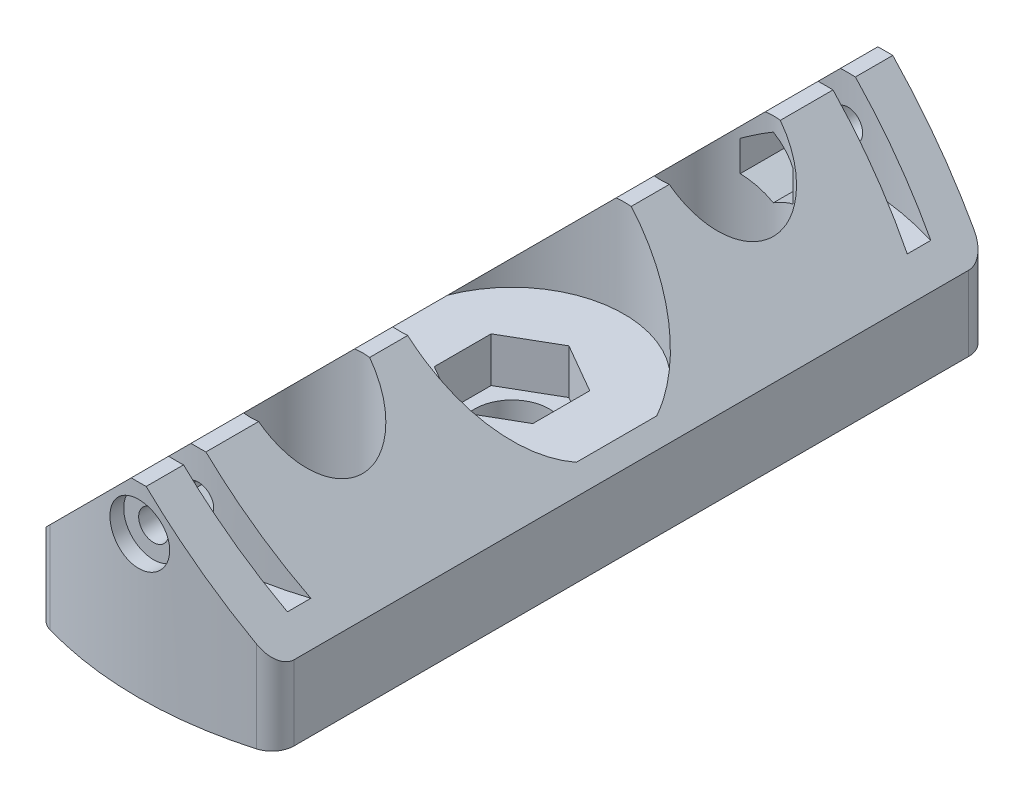
SolidWorks part; units mm, degrees
material "3D printed plastic"
ref_plane "Front Plane" through (0, 0, 0) normal (0, 0, 1) x (1, 0, 0)
ref_plane "Top Plane" through (0, 0, 0) normal (0, 1, 0) x (1, 0, 0)
ref_plane "Right Plane" through (0, 0, 0) normal (1, 0, 0) x (0, 0, -1)
sketch "Sketch1" plane through (0, 0, 0) normal (0, 1, 0) x (1, 0, 0)
  line L0 (0, 27.5) -> (0, -27.5) construction
  line L1 (-16, 45.1664) -> (-16, -45.1664)
  line L2 (16, 45.1664) -> (16, -45.1664)
  circle A0 centre (0, 0) radius 5
  circle A1 centre (0, -27.5) radius 6
  circle A2 centre (0, 27.5) radius 6
  arc A3 (13.8298, 48.0493) -> (-13.8298, 48.0493) centre (0, 0) ccw
  arc A4 (-13.8298, -48.0493) -> (13.8298, -48.0493) centre (0, 0) ccw
  arc A5 (16, -45.1664) -> (13.8298, -48.0493) centre (13, -45.1664) cw
  arc A6 (-16, -45.1664) -> (-13.8298, -48.0493) centre (-13, -45.1664) ccw
  arc A7 (16, 45.1664) -> (13.8298, 48.0493) centre (13, 45.1664) ccw
  arc A8 (-16, 45.1664) -> (-13.8298, 48.0493) centre (-13, 45.1664) cw
  point P15 (-16, -47.3709)
  dimension "D1" = 12
  dimension "D2" = 10
  dimension "D4" = 100
  dimension "D5" = 32
  dimension "D6" = 3
  dimension "D3" = 55
extrude "Boss-Extrude1" add sketch "Sketch1" along normal blind 25
sketch "Sketch2" plane through (0, 25, 0) normal (0, 1, 0) x (1, 0, 0)
  circle A0 centre (0, 27.5) radius 7.5
  circle A2 centre (0, -27.5) radius 7.5
  dimension "D1" = 15
extrude "Cut-Extrude1" cut sketch "Sketch2" against normal blind 24
sketch "Sketch3" plane through (0, 25, 0) normal (0, 1, 0) x (1, 0, 0)
  circle A0 centre (0, 0) radius 15
  dimension "D1" = 30
extrude "Cut-Extrude2" cut sketch "Sketch3" against normal offset from surface (13 mm away) 12 up to face at (0, 0, 33.5)
sketch "Sketch4" plane through (0, 12, 0) normal (0, 1, 0) x (1, 0, 0)
  line L1 (0, 7.621) -> (-6.6, 3.8105)
  line L2 (-6.6, 3.8105) -> (-6.6, -3.8105)
  line L3 (-6.6, -3.8105) -> (0, -7.621)
  line L4 (0, -7.621) -> (6.6, -3.8105)
  line L5 (6.6, -3.8105) -> (6.6, 3.8105)
  line L6 (6.6, 3.8105) -> (0, 7.621)
  circle A0 centre (0, 0) radius 6.6 construction
  dimension "D1" = 13.2
extrude "Cut-Extrude3" cut sketch "Sketch4" against normal blind 6
sketch "Sketch5" plane through (0, 25, 0) normal (0, 1, 0) x (1, 0, 0)
  circle A0 centre (0, 0) radius 45
  dimension "D1" = 90
extrude "Cut-Extrude-Thin1" cut sketch "Sketch5" against normal blind 12 thin thin type one direction reverse wall 3
chamfer "Chamfer1" distance 15 angle 45 2 edges at (-16, 25, 0) (16, 25, 0)
ref_plane "Plane1" through (0, 0, 50) normal (0, 0, 1) x (1, 0, 0)
sketch "Sketch6" plane through (0, 0, 50) normal (0, 0, 1) x (1, 0, 0)
  line L0 (1, 25) -> (-1, 25) construction
  line L1 (0, 19) -> (0, 0) construction
  circle A0 centre (0, 19) radius 4
  dimension "D1" = 8
  dimension "D2" = 6
extrude "Cut-Extrude4" cut sketch "Sketch6" against normal blind 2
sketch "Sketch7" plane through (0, 0, 48) normal (0, 0, 1) x (1, 0, 0)
  circle A0 centre (0, 19) radius 2
  dimension "D1" = 4
extrude "Cut-Extrude5" cut sketch "Sketch7" against normal blind 20
sketch "Sketch8" plane through (0, 0, 48) normal (0, 0, 1) x (1, 0, 0)
  line L1 (0, 14.9008) -> (3.55, 16.9504)
  line L2 (3.55, 16.9504) -> (3.55, 21.0496)
  line L3 (3.55, 21.0496) -> (0, 23.0992)
  line L4 (0, 23.0992) -> (-3.55, 21.0496)
  line L5 (-3.55, 21.0496) -> (-3.55, 16.9504)
  line L6 (-3.55, 16.9504) -> (0, 14.9008)
  circle A0 centre (0, 19) radius 3.55 construction
  dimension "D1" = 7.1
extrude "Cut-Extrude6" cut sketch "Sketch8" against normal up to next from offset 7.5 offset against normal yes
mirror "Mirror1" about plane through (0, 0, 0) normal (0, 0, 1) of "Cut-Extrude6", "Cut-Extrude5", "Cut-Extrude4"
